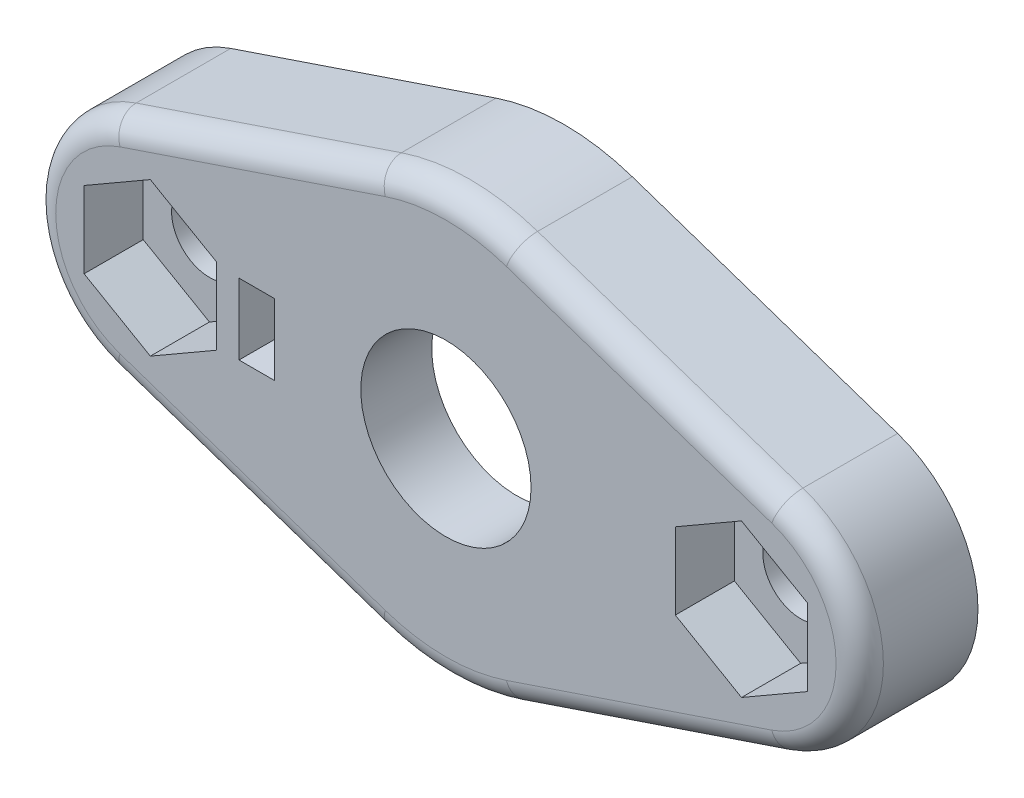
SolidWorks part; units mm, degrees
ref_plane "Спереди" through (0, 0, 0) normal (0, 0, 1) x (1, 0, 0)
ref_plane "Сверху" through (0, 0, 0) normal (0, 1, 0) x (1, 0, 0)
ref_plane "Справа" through (0, 0, 0) normal (1, 0, 0) x (0, 0, -1)
sketch "Эскиз1" plane through (0, 0, 0) normal (0, 0, 1) x (1, 0, 0)
  line L0 (-12.5, 0) -> (12.5, 0) construction
  line L1 (-14.1, 4.7371) -> (-2.88, 8.5268)
  line L2 (-2.88, -8.5268) -> (-14.1, -4.7371)
  line L3 (14.1, -4.7371) -> (2.88, -8.5268)
  line L4 (14.1, 4.7371) -> (2.88, 8.5268)
  line L6 (-8.75, 1.5) -> (-7.25, 1.5)
  line L7 (-8.75, 1.5) -> (-8.75, -1.5)
  line L8 (-8.75, -1.5) -> (-7.25, -1.5)
  line L9 (-7.25, 1.5) -> (-7.25, -1.5)
  line L10 (-8.75, 1.5) -> (-7.25, -1.5) construction
  line L11 (-8.75, -1.5) -> (-7.25, 1.5) construction
  circle A0 centre (0, 0) radius 3.6
  circle A1 centre (-12.5, 0) radius 1.6
  circle A2 centre (12.5, 0) radius 1.6
  arc A3 (-14.1, 4.7371) -> (-14.1, -4.7371) centre (-12.5, 0) ccw
  arc A4 (14.1, 4.7371) -> (14.1, -4.7371) centre (12.5, 0) cw
  arc A5 (-2.88, 8.5268) -> (2.88, 8.5268) centre (0, 0) cw
  arc A6 (-2.88, -8.5268) -> (2.88, -8.5268) centre (0, 0) ccw
  circle A7 centre (0, 0) radius 7.6
  point P16 (-8, 0)
  dimension "D2" = 3.2
  dimension "D3" = 9
  dimension "D4" = 5
  dimension "D5" = 7.2
  dimension "D6" = 15.2
  dimension "D7" = 3
  dimension "D1" = 25
  dimension "D8" = 1.5
  dimension "D9" = 8
extrude "Бобышка-Вытянуть1" add sketch "Эскиз1" along normal blind 5 contours L4 A5 L1 A3 L2 A6 L3 A4
extrude "Вырез-Вытянуть1" cut sketch "Эскиз1<3>" along normal blind 2 contours A7
sketch "Эскиз1<3>" plane through (0, 0, 0) normal (0, 0, 1) x (1, 0, 0) same geometry as "Эскиз1"
extrude "Вырез-Вытянуть2" cut sketch "Эскиз1<4>" along normal blind 5 contours A0 | A2 | A1
sketch "Эскиз1<4>" plane through (0, 0, 0) normal (0, 0, 1) x (1, 0, 0) same geometry as "Эскиз1"
extrude "Вырез-Вытянуть3" cut sketch "Эскиз1<5>" against normal blind 2.5 from surface contours L9 L8 L7 L6 starting at face at (-10.9, 0, 5)
sketch "Эскиз1<5>" plane through (0, 0, 0) normal (0, 0, 1) x (1, 0, 0) same geometry as "Эскиз1"
sketch "Эскиз2" plane through (0, 0, 5) normal (0, 0, 1) x (1, 0, 0)
  line L1 (-12.5, 3.2332) -> (-15.3, 1.6166)
  line L2 (-15.3, 1.6166) -> (-15.3, -1.6166)
  line L3 (-15.3, -1.6166) -> (-12.5, -3.2332)
  line L4 (-12.5, -3.2332) -> (-9.7, -1.6166)
  line L5 (-9.7, -1.6166) -> (-9.7, 1.6166)
  line L6 (-9.7, 1.6166) -> (-12.5, 3.2332)
  line L7 (12.5, 3.2332) -> (9.7, 1.6166)
  line L8 (9.7, 1.6166) -> (9.7, -1.6166)
  line L9 (9.7, -1.6166) -> (12.5, -3.2332)
  line L10 (12.5, -3.2332) -> (15.3, -1.6166)
  line L11 (15.3, -1.6166) -> (15.3, 1.6166)
  line L12 (15.3, 1.6166) -> (12.5, 3.2332)
  circle A0 centre (-12.5, 0) radius 2.8 construction
  circle A1 centre (12.5, 0) radius 2.8 construction
  dimension "D1" = 5.6
extrude "Вырез-Вытянуть4" cut sketch "Эскиз2" against normal blind 2.5
fillet "Скругление1" radius 1 8 edges at (17.5, 0, 5) (8.49, -6.6319, 5) (0, -9, 5) (-8.49, -6.6319, 5) (-17.5, 0, 5) (-8.49, 6.6319, 5) (0, 9, 5) (8.49, 6.6319, 5)
